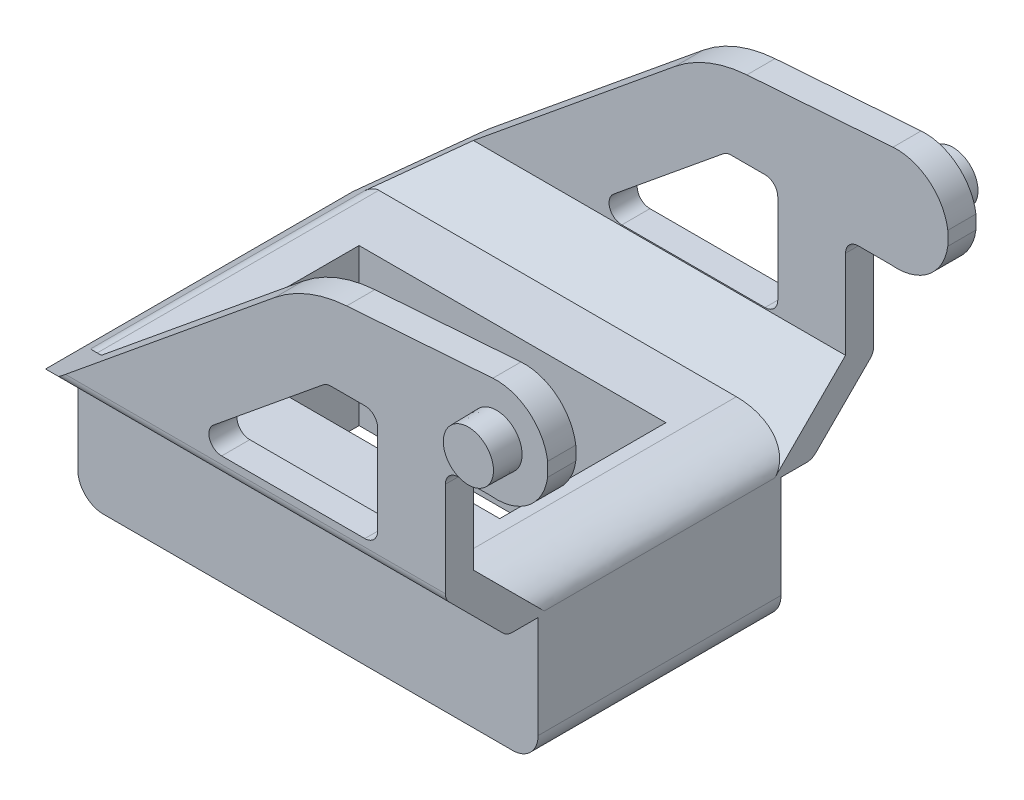
SolidWorks part; units mm, degrees
ref_plane "Front Plane" through (0, 0, 0) normal (0, 0, 1) x (1, 0, 0)
ref_plane "Top Plane" through (0, 0, 0) normal (0, 1, 0) x (1, 0, 0)
ref_plane "Right Plane" through (0, 0, 0) normal (1, 0, 0) x (0, 0, -1)
sketch "Sketch1" plane through (0, 0, 0) normal (0, 1, 0) x (1, 0, 0)
  line L1 (-18, 9.5) -> (18, 9.5)
  line L2 (-18, 9.5) -> (-18, -9.5)
  line L3 (-18, -9.5) -> (18, -9.5)
  line L4 (18, 9.5) -> (18, -9.5)
  line L5 (-18, 9.5) -> (18, -9.5) construction
  line L6 (-18, -9.5) -> (18, 9.5) construction
  point P0 (0, 0)
  dimension "D1" = 36
  dimension "D2" = 19
extrude "Boss-Extrude1" add sketch "Sketch1" along normal blind 10
sketch "Sketch2" plane through (0, 10, 0) normal (0, 1, 0) x (1, 0, 0)
  line L0 (18, 9.5) -> (-18, 9.5) construction
  line L1 (-12, 6.5) -> (12, 6.5)
  line L2 (-12, 6.5) -> (-12, -6.5)
  line L3 (-12, -6.5) -> (12, -6.5)
  line L4 (12, 6.5) -> (12, -6.5)
  line L5 (-12, 6.5) -> (12, -6.5) construction
  line L6 (-12, -6.5) -> (12, 6.5) construction
  line L7 (18, -9.5) -> (18, 9.5) construction
  point P0 (0, 0)
  dimension "D1" = 3
  dimension "D2" = 6
extrude "Cut-Extrude1" cut sketch "Sketch2" against normal blind 10
sketch "Sketch3" plane through (0, 10, 0) normal (0, 1, 0) x (1, 0, 0)
  line L0 (-18, 9.5) -> (-18, -9.5) construction
  line L1 (26, -16.75) -> (-18, -16.75)
  line L2 (26, -16.75) -> (26, 16.75)
  line L3 (26, 16.75) -> (-18, 16.75)
  line L4 (-18, -16.75) -> (-18, 16.75)
  line L5 (26, -16.75) -> (-18, 16.75) construction
  line L6 (26, 16.75) -> (-18, -16.75) construction
  line L7 (-3.3762, 0) -> (2.2252, 0) construction
  point P0 (4, 0)
  dimension "D1" = 33.5
  dimension "D2" = 44
extrude "Boss-Extrude2" add sketch "Sketch3" along normal blind 22
sketch "Sketch5" plane through (-18, 0, 0) normal (-1, 0, 0) x (0, 0, 1)
  line L0 (0, -0.7799) -> (0, 26.9552) construction
  line L1 (-16.75, 32) -> (-16.75, 10) construction
  line L2 (-14.55, 32) -> (14.55, 32)
  line L3 (-14.55, 32) -> (-14.55, 15.7355)
  line L4 (-11.0145, 12.2) -> (11.0145, 12.2)
  line L5 (14.55, 32) -> (14.55, 15.7355)
  line L6 (-14.55, 32) -> (14.55, 12.2) construction
  line L7 (-14.55, 12.2) -> (14.55, 32) construction
  line L8 (9.5, 10) -> (16.75, 10) construction
  line L9 (11.0145, 12.2) -> (14.55, 15.7355)
  line L10 (-3.0817, 22.1) -> (4.1463, 22.1) construction
  line L11 (-11.0145, 12.2) -> (-14.55, 15.7355)
  line L12 (-16.75, 32) -> (16.75, 32) construction
  point P3 (0, 22.1)
  point P14 (12.7822, 13.9678)
  dimension "D1" = 2.2
  dimension "D2" = 2.2
  dimension "D3" = 45
  dimension "D4" = 2.5
extrude "Cut-Extrude2" cut sketch "Sketch5" against normal up to next
sketch "Sketch7" plane through (-18, 0, 0) normal (-1, 0, 0) x (0, 0, 1)
  line L0 (-16.75, 14.8243) -> (-11.9257, 10)
  line L1 (-16.75, 32) -> (-16.75, 10) construction
  line L2 (-16.75, 10) -> (-9.5, 10) construction
  line L3 (-14.55, 15.7355) -> (-11.0145, 12.2) construction
  line L4 (0, 8.8131) -> (0, 22.0107) construction
  line L5 (16.75, 14.8243) -> (11.9257, 10)
  line L6 (-16.75, 14.8243) -> (-16.75, 10)
  line L7 (-16.75, 10) -> (-11.9257, 10)
  line L8 (11.9257, 10) -> (16.75, 10)
  line L9 (16.75, 10) -> (16.75, 14.8243)
  dimension "D1" = 2.2
extrude "Cut-Extrude3" cut sketch "Sketch7" against normal up to next
sketch "Sketch9" plane through (0, 0, 16.75) normal (0, 0, 1) x (1, 0, 0)
  line L0 (12.7, 23.8243) -> (12.7, 16.8243)
  line L1 (11.7, 15.8243) -> (0.5014, 15.8243)
  line L2 (-0.1318, 17.5982) -> (8.4237, 24.5982)
  line L3 (9.057, 24.8243) -> (11.7, 24.8243)
  line L4 (26, 14.8243) -> (-18, 14.8243) construction
  line L7 (18, 10) -> (18, 0) construction
  arc A0 (0.5014, 15.8243) -> (-0.1318, 17.5982) centre (0.5014, 16.8243) cw
  arc A1 (8.4237, 24.5982) -> (9.057, 24.8243) centre (9.057, 23.8243) cw
  arc A2 (12.7, 23.8243) -> (11.7, 24.8243) centre (11.7, 23.8243) ccw
  arc A3 (12.7, 16.8243) -> (11.7, 15.8243) centre (11.7, 16.8243) cw
  point P10 (-2.3, 15.8243)
  point P13 (8.7, 24.8243)
  point P16 (12.7, 24.8243)
  point P19 (12.7, 15.8243)
  dimension "D6" = 1
  dimension "D1" = 5.3
  dimension "D2" = 1
  dimension "D3" = 9
  dimension "D4" = 15
  dimension "D5" = 4
extrude "Cut-Extrude4" cut sketch "Sketch9" against normal through all
sketch "Sketch10" plane through (0, 0, 16.75) normal (0, 0, 1) x (1, 0, 0)
  line L0 (-18, 10.0985) -> (4.6628, 28.6409)
  line L1 (10.2818, 30.8758) -> (26, 32)
  line L2 (8.4237, 24.5982) -> (-0.1318, 17.5982) construction
  line L3 (-18, 32) -> (26, 32) construction
  line L4 (-18, 32) -> (-18, 14.8243) construction
  line L5 (-18, 32) -> (26, 32)
  line L6 (-18, 32) -> (-18, 10.0985)
  arc A0 (4.6628, 28.6409) -> (10.2818, 30.8758) centre (10.9952, 20.9013) cw
  point P7 (0.7887, 30.1968)
  dimension "D1" = 10
extrude "Cut-Extrude6" cut sketch "Sketch10" against normal through all
sketch "Sketch11" plane through (0, 0, 16.75) normal (0, 0, 1) x (1, 0, 0)
  line L0 (18, 6.9264) -> (18, 35.296) construction
  line L1 (18, 10) -> (18, 0) construction
  line L2 (18, 10) -> (18, 22.6539)
  line L3 (19, 23.6539) -> (21.5679, 23.6539)
  line L4 (18, 31.4278) -> (21.712, 31.6933)
  line L5 (10.2818, 30.8758) -> (26, 32) construction
  line L6 (18, 31.4278) -> (18, 34.0614)
  line L7 (18, 34.0614) -> (30.2083, 34.9345)
  line L8 (30.2083, 34.9345) -> (29.248, 10)
  line L9 (29.248, 10) -> (18, 10)
  arc A0 (21.712, 31.6933) -> (21.5679, 23.6539) centre (22, 27.6671) cw
  arc A1 (18, 22.6539) -> (19, 23.6539) centre (19, 22.6539) cw
  point P15 (0, 0)
  point P19 (18, 23.6539)
  dimension "D2" = 1
  dimension "D1" = 4
extrude "Cut-Extrude7" cut sketch "Sketch11" against normal through all
sketch "Sketch12" plane through (0, 0, 16.75) normal (0, 0, 1) x (1, 0, 0)
  circle A0 centre (22, 27.6671) radius 2
  arc A1 (26, 28.2085) -> (21.712, 31.6933) centre (22, 27.6671) ccw construction
  dimension "D1" = 4
extrude "Boss-Extrude3" add sketch "Sketch12" along normal blind 2.2 draft 1
mirror "Mirror1" about plane through (0, 0, 0) normal (0, 0, 1) of "Boss-Extrude3"
sketch "Sketch13" plane through (0, 10, 0) normal (0, -1, 0) x (1, 0, 0)
  line L4 (12, -6.5) -> (12, 6.5)
  line L5 (12, 6.5) -> (-12, 6.5)
  line L6 (-12, 6.5) -> (-12, -6.5)
  line L7 (-12, -6.5) -> (12, -6.5)
  line L8 (12, -6.5) -> (12, 6.5)
  line L9 (12, 6.5) -> (-12, 6.5)
  line L10 (-12, 6.5) -> (-12, -6.5)
  line L11 (-12, -6.5) -> (12, -6.5)
  dimension "D1" = 0
extrude "Cut-Extrude8" cut sketch "Sketch13" against normal up to next
fillet "Fillet1" radius 2 2 edges at (18, 0, 0) (-18, 0, 0)
fillet "Fillet2" radius 1 4 edges at (2.8879, 14.8243, -16.75) (2.8879, 14.8243, 16.75) (0, 10, -11.9257) (0, 10, 11.9257)
fillet "Fillet4" radius 2 1 edges at (18, 12.2, 0) second distance 5 first distance on face at (18, 13.5207, 0)
fillet "Fillet5" radius 1.3 1 edges at (-15.4316, 12.2, 0)
